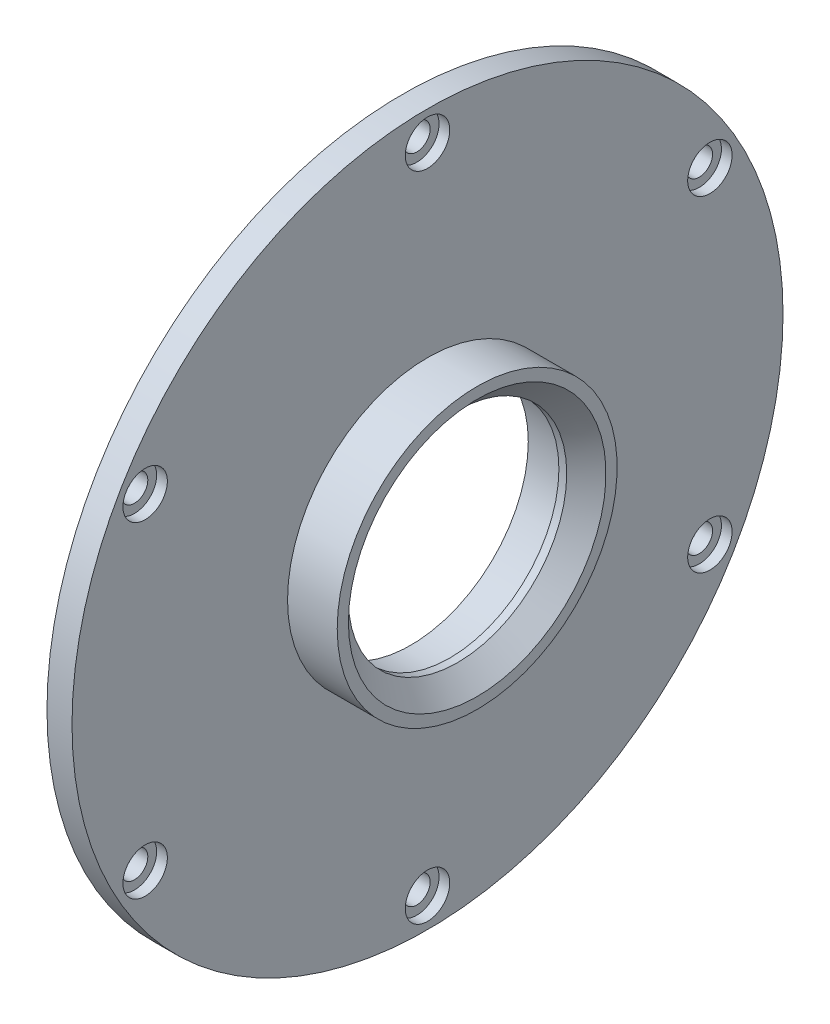
SolidWorks part; units mm, degrees
ref_plane "Front Plane" through (0, 0, 0) normal (0, 0, 1) x (1, 0, 0)
ref_plane "Top Plane" through (0, 0, 0) normal (0, 1, 0) x (1, 0, 0)
ref_plane "Right Plane" through (0, 0, 0) normal (1, 0, 0) x (0, 0, -1)
sketch "Sketch2" plane through (0, 0, 0) normal (0, 0, 1) x (1, 0, 0)
  line L0 (0, 0) -> (58.591, 0) construction
  line L2 (0, 0) -> (18.4, 0)
  line L3 (0, 0) -> (0, 2.5)
  line L4 (0, 2.5) -> (18.4, 2.5)
  line L5 (18.4, 0) -> (18.4, 2.5)
  line L6 (6.0094, 2.5) -> (6.0094, 6)
  line L11 (6.0094, 6) -> (9.9794, 6)
  line L16 (12.9794, 6) -> (12.9794, 3)
  line L17 (12.9794, 3) -> (13.6398, 3)
  line L18 (13.6398, 3) -> (13.6398, 2.5)
  line L19 (13.6398, 2.5) -> (6.0094, 2.5)
  line L22 (13.6398, 2.5) -> (16.1198, 2.5)
  line L23 (13.6398, 2.5) -> (13.6398, 4)
  line L24 (13.6398, 4) -> (16.1198, 4)
  line L25 (16.1198, 2.5) -> (16.1198, 4)
  line L27 (6.0094, 6) -> (9.9794, 6)
  line L28 (6.0094, 6) -> (6.0094, 9)
  line L29 (6.0094, 9) -> (9.9794, 9)
  line L30 (9.9794, 6) -> (9.9794, 9)
  line L31 (6.0094, 9) -> (6.0094, 8.25)
  line L32 (6.0094, 8.25) -> (5.0094, 8.25)
  line L33 (8.6609, 22.001) -> (8.6609, 12.476) construction
  line L34 (5.0094, 12.476) -> (12.3124, 12.476)
  line L35 (9.9794, 9) -> (12.3124, 9)
  line L36 (5.0094, 7.9375) -> (1.8344, 7.9375)
  line L37 (5.0094, 8.25) -> (5.0094, 12.476)
  line L38 (5.0094, 7.9375) -> (5.0094, 13.9365)
  line L39 (5.0094, 13.9365) -> (1.8344, 13.9365)
  line L40 (1.8344, 7.9375) -> (1.8344, 13.9365)
  line L41 (5.0094, 22.001) -> (12.3124, 22.001)
  line L42 (5.0094, 22.001) -> (5.0094, 30.1625)
  line L43 (5.0094, 30.1625) -> (12.3124, 30.1625)
  line L44 (12.3124, 22.001) -> (12.3124, 30.1625)
  line L49 (16.6398, 22.001) -> (16.6398, 7.5)
  line L51 (23.0198, 7.5) -> (23.0198, 6.5)
  line L54 (16.1198, 4) -> (13.6398, 4)
  line L56 (18.0398, 7.5) -> (23.0198, 7.5)
  line L57 (13.3124, 22.001) -> (16.6398, 22.001)
  line L58 (16.1198, 3.5) -> (20.0198, 3.5)
  line L59 (29.9098, 14) -> (26.9098, 11)
  line L60 (4.0094, 31.75) -> (18.0398, 31.75)
  line L61 (18.0398, 7.5) -> (23.0198, 7.5)
  line L62 (18.0398, 7.5) -> (18.0398, 12)
  line L63 (18.0398, 12) -> (23.0198, 12)
  line L64 (23.0198, 7.5) -> (23.0198, 12)
  line L65 (18.0398, 31.75) -> (18.0398, 12)
  line L66 (23.0198, 11) -> (26.9098, 11)
  line L67 (34.8098, 23) -> (31.3098, 19.5)
  line L68 (35.8098, 31) -> (38.7998, 33.99)
  line L69 (29.9098, 14) -> (29.9098, 15)
  line L70 (29.9098, 15) -> (22.9398, 15)
  line L71 (22.9398, 15) -> (21.0398, 15)
  line L72 (18.0398, 7.5) -> (16.6398, 7.5)
  line L73 (21.0398, 15) -> (21.0398, 43)
  line L74 (19.5798, 40) -> (9.6198, 40)
  line L75 (9.6198, 40) -> (4.0094, 40)
  line L76 (21.0398, 43) -> (19.5798, 43)
  line L77 (22.9398, 15) -> (29.9098, 15)
  line L78 (22.9398, 15) -> (22.9398, 21)
  line L79 (22.9398, 21) -> (29.9098, 21)
  line L80 (29.9098, 15) -> (29.9098, 21)
  line L81 (9.6198, 40) -> (19.5798, 40)
  line L82 (9.6198, 40) -> (9.6198, 50)
  line L83 (9.6198, 50) -> (19.5798, 50)
  line L84 (19.5798, 40) -> (19.5798, 50)
  line L85 (4.0094, 40) -> (4.0094, 31.75)
  line L86 (12.9794, 3) -> (12.9794, 2.5)
  line L87 (31.3098, 19.5) -> (29.9098, 19.5)
  line L88 (21.4694, 63.5) -> (21.4694, 51.308)
  line L89 (21.4694, 63.5) -> (25.9398, 63.5)
  line L90 (25.9398, 63.5) -> (25.9398, 25)
  line L91 (27.8398, 25) -> (25.9398, 25)
  line L92 (9.6198, 48) -> (8.1598, 48)
  line L93 (8.1598, 48) -> (8.1598, 53.476)
  line L94 (8.1598, 53.476) -> (19.5798, 53.476)
  line L95 (19.5798, 53.476) -> (19.5798, 50)
  line L96 (13.8698, 63.001) -> (13.8698, 53.476) construction
  line L97 (8.1598, 63.001) -> (19.5798, 63.001)
  line L98 (8.1598, 63.001) -> (8.1598, 68.2625)
  line L99 (8.1598, 68.2625) -> (19.5798, 68.2625)
  line L100 (19.5798, 63.001) -> (19.5798, 68.2625)
  line L101 (12.9794, 6) -> (11.9794, 6)
  line L102 (8.1598, 44.825) -> (4.9848, 44.825)
  line L103 (8.1598, 44.825) -> (8.1598, 54.9365)
  line L104 (8.1598, 54.9365) -> (4.9848, 54.9365)
  line L106 (9.9794, 6) -> (10.8794, 6)
  line L107 (27.8398, 25) -> (34.8098, 25)
  line L108 (34.8098, 25) -> (34.8098, 23)
  line L109 (0, 0) -> (-2, 0)
  line L110 (0, 0) -> (0, 11)
  line L111 (27.8398, 25) -> (34.8098, 25)
  line L112 (27.8398, 25) -> (27.8398, 32.5)
  line L113 (27.8398, 32.5) -> (34.8098, 32.5)
  line L114 (34.8098, 25) -> (34.8098, 32.5)
  line L115 (35.8098, 31) -> (34.8098, 31)
  line L116 (27.8398, 32.5) -> (27.8398, 64.5)
  line L117 (20.5373, 74.025) -> (6.2023, 74.025)
  line L118 (6.2023, 74.025) -> (6.2023, 76.2)
  line L119 (38.7998, 47.29) -> (30.8398, 55.25)
  line L120 (0, 11) -> (-2, 11)
  line L121 (38.7998, 43.815) -> (30.8623, 43.815)
  line L123 (-4.8152, 69.85) -> (1.5348, 76.2)
  line L124 (38.7998, 47.29) -> (38.7998, 33.99)
  line L125 (-2, 0) -> (-2, 11)
  line L126 (38.7998, 37.465) -> (30.8623, 37.465)
  line L127 (30.8623, 43.815) -> (30.8623, 37.465)
  line L128 (6.0094, 2.5) -> (6.0094, 0)
  line L129 (-0.0152, 63.5) -> (-0.0152, 30)
  line L132 (4.9848, 63.5) -> (-0.0152, 63.5)
  line L136 (-1.8152, 30) -> (-11.7752, 30)
  line L138 (-13.7752, 25.4) -> (-2, 25.4)
  line L139 (-2, 25.4) -> (-2, 11.5)
  line L140 (27.8398, 64.5) -> (20.5373, 64.5)
  line L141 (-1.8152, 30) -> (-11.7752, 30)
  line L142 (-1.8152, 30) -> (-1.8152, 39)
  line L143 (-1.8152, 39) -> (-11.7752, 39)
  line L144 (-11.7752, 30) -> (-11.7752, 39)
  line L145 (20.5373, 64.5) -> (20.5373, 74.025)
  line L146 (-12.7752, 37) -> (-12.7752, 47.29)
  line L147 (-12.7752, 37) -> (-11.7752, 37)
  line L148 (30.8398, 55.25) -> (30.8398, 76.2)
  line L149 (11.9794, 6) -> (11.9794, 5.45)
  line L154 (-2, 11.5) -> (0.5, 11.5)
  line L155 (4.9848, 60.6197) -> (24.0348, 60.6197)
  line L160 (4.9848, 60.6197) -> (4.9848, 55.8572)
  line L161 (4.9848, 55.8572) -> (24.0348, 55.8572)
  line L166 (24.0348, 60.6197) -> (24.0348, 55.8572)
  line L167 (4.9848, 60.6197) -> (24.0348, 55.8572) construction
  line L172 (4.9848, 55.8572) -> (24.0348, 60.6197) construction
  line L173 (24.0348, 62.2072) -> (25.9398, 62.2072)
  line L174 (11.9794, 5.45) -> (10.8794, 5.45)
  line L175 (10.8794, 6) -> (10.8794, 5.45)
  line L176 (24.0348, 62.2072) -> (24.0348, 54.2697)
  line L177 (24.0348, 54.2697) -> (25.9398, 54.2697)
  line L178 (25.9398, 62.2072) -> (25.9398, 54.2697)
  line L179 (24.0348, 62.2072) -> (25.9398, 54.2697) construction
  line L180 (24.0348, 54.2697) -> (25.9398, 62.2072) construction
  line L181 (3, 19.6197) -> (15.7, 19.6197)
  line L182 (3, 19.6197) -> (3, 14.8572)
  line L183 (3, 14.8572) -> (15.7, 14.8572)
  line L184 (15.7, 19.6197) -> (15.7, 14.8572)
  line L185 (3, 19.6197) -> (15.7, 14.8572) construction
  line L186 (3, 14.8572) -> (15.7, 19.6197) construction
  line L187 (15.7, 21.2072) -> (16.6398, 21.2072)
  line L188 (15.7, 21.2072) -> (15.7, 13.2697)
  line L189 (15.7, 13.2697) -> (16.6398, 13.2697)
  line L190 (16.6398, 21.2072) -> (16.6398, 13.2697)
  line L191 (15.7, 21.2072) -> (16.6398, 13.2697) construction
  line L192 (15.7, 13.2697) -> (16.6398, 21.2072) construction
  line L193 (0.5, 11.5) -> (0.5, 6.9375)
  line L194 (0.5, 6.9375) -> (1.8344, 6.9375)
  line L195 (23.0198, 6.5) -> (20.0198, 3.5)
  line L196 (4.9848, 63.5) -> (4.9848, 54.9365)
  line L197 (3, 43.825) -> (4.9848, 43.825)
  line L198 (1.8344, 6.9375) -> (1.8344, 7.9375)
  line L199 (6.0094, 0) -> (12.9794, 0)
  line L200 (12.9794, 0) -> (12.9794, 2.5)
  line L201 (18.0398, 31.75) -> (18.0398, 35.875)
  line L202 (18.0398, 35.875) -> (21.0398, 35.875)
  line L203 (30.8398, 76.2) -> (6.2023, 76.2)
  line L204 (2.7573, 69.85) -> (7.2023, 69.85) construction
  line L205 (7.2023, 67.4688) -> (26.2523, 67.4688)
  line L206 (7.2023, 74.025) -> (7.2023, 64.5)
  line L207 (7.2023, 64.5) -> (-1.8152, 64.5)
  line L208 (-1.8152, 64.5) -> (-1.8152, 39)
  line L209 (-12.7752, 47.29) -> (-4.8152, 55.25)
  line L210 (-4.8152, 55.25) -> (-4.8152, 69.85)
  line L211 (7.2023, 67.4688) -> (7.2023, 72.2312)
  line L212 (7.2023, 72.2312) -> (26.2523, 72.2313)
  line L213 (26.2523, 67.4688) -> (26.2523, 72.2313)
  line L214 (26.2523, 73.8187) -> (30.8398, 73.8187)
  line L215 (26.2523, 73.8187) -> (26.2523, 65.8813)
  line L216 (26.2523, 65.8813) -> (30.8398, 65.8813)
  line L217 (30.8398, 73.8187) -> (30.8398, 65.8813)
  line L218 (2.7573, 72.2313) -> (24.9823, 72.2313)
  line L219 (2.7573, 72.2313) -> (2.7573, 67.4687)
  line L220 (2.7573, 67.4687) -> (24.9823, 67.4687)
  line L221 (24.9823, 72.2313) -> (24.9823, 67.4687)
  line L222 (24.9823, 69.85) -> (20.5373, 69.85) construction
  line L223 (21.4694, 51.308) -> (22.9398, 51.308)
  line L224 (22.9398, 51.308) -> (22.9398, 21)
  line L225 (13.6398, 4) -> (13.6398, 12.2697)
  line L226 (13.6398, 12.2697) -> (13.3124, 12.2697)
  line L227 (13.3124, 12.2697) -> (13.3124, 22.001)
  line L228 (12.3124, 9) -> (12.3124, 12.476)
  line L229 (-1.8152, 30) -> (-0.0152, 30)
  line L230 (8.1598, 65.6317) -> (2.7573, 65.6317) construction
  line L231 (19.5798, 65.6317) -> (24.9823, 65.6317) construction
  line L232 (1.5348, 76.2) -> (6.2023, 76.2)
  line L233 (-11.7752, 30) -> (-13.7752, 30)
  line L234 (-13.7752, 30) -> (-13.7752, 25.4)
  line L235 (3, 13.9365) -> (3, 43.825)
  line L236 (4.9848, 54.9365) -> (4.9848, 44.825)
  line L237 (4.9848, 43.825) -> (4.9848, 44.825)
  circle A0 centre (26.8898, 25.95) radius 0.95
  circle A1 centre (21.9898, 15.95) radius 0.95
  circle A2 centre (17.3398, 8.2) radius 0.7
  circle A3 centre (10.4294, 6.45) radius 0.45
  circle A4 centre (-0.9152, 30.9) radius 0.9
  point P7 (24.9873, 58.2385)
  point P131 (16.1699, 17.2385)
  point P135 (14.5098, 58.2385)
  point P146 (9.35, 17.2385)
sketch "Sketch3" plane through (0, 0, 0) normal (0, 0, 1) x (1, 0, 0)
  line L0 (34.8098, 25) -> (34.8098, 23) construction
  line L4 (29.9098, 15) -> (29.9098, 21) construction
  line L5 (31.3098, 19.5) -> (29.9098, 19.5) construction
  line L6 (34.8098, 23) -> (31.3098, 19.5) construction
  line L7 (22.9398, 21) -> (29.9098, 21) construction
  line L11 (34.8098, 25) -> (34.8098, 23)
  line L15 (29.9098, 19.5) -> (29.9098, 21)
  line L16 (31.3098, 19.5) -> (29.9098, 19.5)
  line L17 (34.8098, 23) -> (31.3098, 19.5)
  line L18 (22.9398, 21) -> (29.9098, 21)
  line L22 (27.8398, 25) -> (25.9398, 25) construction
  line L23 (27.8398, 25) -> (34.8098, 25) construction
  line L24 (25.9398, 63.5) -> (25.9398, 25) construction
  line L25 (22.9398, 51.308) -> (22.9398, 21) construction
  line L26 (21.4694, 51.308) -> (22.9398, 51.308) construction
  line L27 (21.4694, 63.5) -> (21.4694, 51.308) construction
  line L28 (21.4694, 63.5) -> (25.9398, 63.5) construction
  line L29 (27.8398, 25) -> (25.9398, 25)
  line L30 (27.8398, 25) -> (34.8098, 25)
  line L31 (25.9398, 63.5) -> (25.9398, 25)
  line L32 (22.9398, 51.308) -> (22.9398, 21)
  line L33 (21.4694, 51.308) -> (22.9398, 51.308)
  line L34 (21.4694, 63.5) -> (21.4694, 51.308)
  line L35 (21.4694, 63.5) -> (25.9398, 63.5)
revolve "Revolve1" add sketch "Sketch3" angle 360 about L0
sketch "Sketch4" plane through (0, 0, 0) normal (1, 0, 0) x (0, 0, -1)
  line L0 (0, 0) -> (0, 69.85) construction
  line L1 (0, 0) -> (13.6271, 68.5079) construction
  line L2 (0, 0) -> (0, 58.2385) construction
  line L3 (0, 0) -> (50.436, 29.1192) construction
  line L4 (0, 0) -> (0, 31.75) construction
  line L5 (0, 0) -> (12.1502, 29.3332) construction
  line L6 (0, 0) -> (0, 17.2385) construction
  line L7 (0, 0) -> (14.929, 8.6192) construction
  line L8 (0, 0) -> (0, 58.2385) construction
  line L9 (0, 0) -> (50.436, 29.1192) construction
  line L10 (0, 0) -> (5.9583, 29.9542) construction
  line L11 (0, 0) -> (16.9677, 25.394) construction
  circle A0 centre (0, 0) radius 69.85 construction
  circle A1 centre (0, 0) radius 58.2385 construction
  circle A2 centre (0, 0) radius 31.75 construction
  circle A3 centre (0, 0) radius 17.2385 construction
  circle A4 centre (0, 69.85) radius 3.175
  circle A5 centre (0, 58.2385) radius 4.7625
  circle A6 centre (0, 31.75) radius 3.175
  circle A7 centre (0, 17.2385) radius 4.7625
  circle A8 centre (13.6271, 68.5079) radius 3.175
  circle A9 centre (26.7304, 64.533) radius 3.175
  circle A10 centre (38.8066, 58.0782) radius 3.175
  circle A11 centre (49.3914, 49.3914) radius 3.175
  circle A12 centre (58.0782, 38.8066) radius 3.175
  circle A13 centre (64.533, 26.7304) radius 3.175
  circle A14 centre (68.5079, 13.6271) radius 3.175
  circle A15 centre (69.85, 0) radius 3.175
  circle A16 centre (68.5079, -13.6271) radius 3.175
  circle A17 centre (64.533, -26.7304) radius 3.175
  circle A18 centre (58.0782, -38.8066) radius 3.175
  circle A19 centre (49.3914, -49.3914) radius 3.175
  circle A20 centre (38.8066, -58.0782) radius 3.175
  circle A21 centre (26.7304, -64.533) radius 3.175
  circle A22 centre (13.6271, -68.5079) radius 3.175
  circle A23 centre (0, -69.85) radius 3.175
  circle A24 centre (-13.6271, -68.5079) radius 3.175
  circle A25 centre (-26.7304, -64.533) radius 3.175
  circle A26 centre (-38.8066, -58.0782) radius 3.175
  circle A27 centre (-49.3914, -49.3914) radius 3.175
  circle A28 centre (-58.0782, -38.8066) radius 3.175
  circle A29 centre (-64.533, -26.7304) radius 3.175
  circle A30 centre (-68.5079, -13.6271) radius 3.175
  circle A31 centre (-69.85, 0) radius 3.175
  circle A32 centre (-68.5079, 13.6271) radius 3.175
  circle A33 centre (-64.533, 26.7304) radius 3.175
  circle A34 centre (-58.0782, 38.8066) radius 3.175
  circle A35 centre (-49.3914, 49.3914) radius 3.175
  circle A36 centre (-38.8066, 58.0782) radius 3.175
  circle A37 centre (-26.7304, 64.533) radius 3.175
  circle A38 centre (-13.6271, 68.5079) radius 3.175
  circle A47 centre (50.436, 29.1192) radius 4.7625
  circle A48 centre (50.436, -29.1192) radius 4.7625
  circle A49 centre (0, -58.2385) radius 4.7625
  circle A50 centre (-50.436, -29.1192) radius 4.7625
  circle A51 centre (-50.436, 29.1192) radius 4.7625
  circle A58 centre (12.1502, 29.3332) radius 3.175
  circle A59 centre (22.4506, 22.4506) radius 3.175
  circle A60 centre (29.3332, 12.1502) radius 3.175
  circle A61 centre (31.75, 0) radius 3.175
  circle A62 centre (29.3332, -12.1502) radius 3.175
  circle A63 centre (22.4506, -22.4506) radius 3.175
  circle A64 centre (12.1502, -29.3332) radius 3.175
  circle A65 centre (0, -31.75) radius 3.175
  circle A66 centre (-12.1502, -29.3332) radius 3.175
  circle A67 centre (-22.4506, -22.4506) radius 3.175
  circle A68 centre (-29.3332, -12.1502) radius 3.175
  circle A69 centre (-31.75, 0) radius 3.175
  circle A70 centre (-29.3332, 12.1502) radius 3.175
  circle A71 centre (-22.4506, 22.4506) radius 3.175
  circle A72 centre (14.929, 8.6192) radius 4.7625
  circle A73 centre (14.929, -8.6192) radius 4.7625
  circle A74 centre (0, -17.2385) radius 4.7625
  circle A75 centre (-14.929, -8.6192) radius 4.7625
  circle A76 centre (-14.929, 8.6192) radius 4.7625
  circle A77 centre (0, 0) radius 50
  circle A78 centre (0, 0) radius 9
  circle A79 centre (-12.1502, 29.3332) radius 3.175
  circle A80 centre (0, 0) radius 76.2
  circle A81 centre (0, 0) radius 74.025
  circle A82 centre (0, 69.85) radius 3.9687
  circle A83 centre (49.3914, 49.3914) radius 3.9687
  circle A84 centre (69.85, 0) radius 3.9688
  circle A85 centre (49.3914, -49.3914) radius 3.9687
  circle A86 centre (0, -69.85) radius 3.9687
  circle A87 centre (-49.3914, -49.3914) radius 3.9687
  circle A88 centre (-69.85, 0) radius 3.9688
  circle A89 centre (-49.3914, 49.3914) radius 3.9687
  circle A90 centre (0, 69.85) radius 2.3812
  circle A91 centre (13.6271, 68.5079) radius 2.3812
  circle A92 centre (26.7304, 64.533) radius 2.3813
  circle A93 centre (38.8066, 58.0782) radius 2.3812
  circle A94 centre (49.3914, 49.3914) radius 2.3812
  circle A95 centre (58.0782, 38.8066) radius 2.3812
  circle A96 centre (64.533, 26.7304) radius 2.3813
  circle A97 centre (68.5079, 13.6271) radius 2.3813
  circle A98 centre (69.85, 0) radius 2.3813
  circle A99 centre (68.5079, -13.6271) radius 2.3813
  circle A100 centre (64.533, -26.7304) radius 2.3813
  circle A101 centre (58.0782, -38.8066) radius 2.3812
  circle A102 centre (49.3914, -49.3914) radius 2.3812
  circle A103 centre (38.8066, -58.0782) radius 2.3812
  circle A104 centre (26.7304, -64.533) radius 2.3813
  circle A105 centre (13.6271, -68.5079) radius 2.3812
  circle A106 centre (0, -69.85) radius 2.3812
  circle A107 centre (-13.6271, -68.5079) radius 2.3812
  circle A108 centre (-26.7304, -64.533) radius 2.3813
  circle A109 centre (-38.8066, -58.0782) radius 2.3812
  circle A110 centre (-49.3914, -49.3914) radius 2.3812
  circle A111 centre (-58.0782, -38.8066) radius 2.3812
  circle A112 centre (-64.533, -26.7304) radius 2.3812
  arc A113 (3.0399, 30.8338) -> (8.9911, 29.65) centre (5.9583, 29.9542) cw
  arc A114 (14.6081, 27.3234) -> (19.6532, 23.9523) centre (16.9677, 25.394) cw
  arc A115 (23.9523, 19.6532) -> (27.3234, 14.6081) centre (25.394, 16.9677) cw
  arc A116 (29.65, 8.9911) -> (30.8338, 3.0399) centre (29.9542, 5.9583) cw
  arc A117 (30.8338, -3.0399) -> (29.65, -8.9911) centre (29.9542, -5.9583) cw
  arc A118 (27.3234, -14.6081) -> (23.9523, -19.6532) centre (25.394, -16.9677) cw
  arc A119 (19.6532, -23.9523) -> (14.6081, -27.3234) centre (16.9677, -25.394) cw
  arc A120 (8.9911, -29.65) -> (3.0399, -30.8338) centre (5.9583, -29.9542) cw
  arc A121 (-3.0399, -30.8338) -> (-8.9911, -29.65) centre (-5.9583, -29.9542) cw
  arc A122 (-14.6081, -27.3234) -> (-19.6532, -23.9523) centre (-16.9677, -25.394) cw
  arc A123 (-23.9523, -19.6532) -> (-27.3234, -14.6081) centre (-25.394, -16.9677) cw
  arc A124 (-29.65, -8.9911) -> (-30.8338, -3.0399) centre (-29.9542, -5.9583) cw
  arc A125 (-30.8338, 3.0399) -> (-29.65, 8.9911) centre (-29.9542, 5.9583) cw
  arc A126 (-27.3234, 14.6081) -> (-23.9523, 19.6532) centre (-25.394, 16.9677) cw
  arc A127 (-19.6532, 23.9523) -> (-14.6081, 27.3234) centre (-16.9677, 25.394) cw
  arc A128 (-8.9911, 29.65) -> (-3.0399, 30.8338) centre (-5.9583, 29.9542) cw
  arc A129 (26.9875, 0) -> (26.9932, 0.1932) centre (30.2705, 0) cw
  arc A130 (65.0988, 0.2771) -> (65.0875, 0) centre (68.4964, 0) ccw
  circle A131 centre (1.5875, 0) radius 40
  circle A132 centre (1.5875, 0) radius 2.5
  circle A133 centre (1.5875, 0) radius 3
  circle A134 centre (1.5875, 0) radius 43
  circle A135 centre (-68.5079, -13.6271) radius 2.3813
  circle A136 centre (-69.85, 0) radius 2.3813
  circle A137 centre (-68.5079, 13.6271) radius 2.3813
  circle A138 centre (-64.533, 26.7304) radius 2.3812
  circle A139 centre (-58.0782, 38.8066) radius 2.3812
  circle A140 centre (-49.3914, 49.3914) radius 2.3812
  circle A141 centre (-38.8066, 58.0782) radius 2.3812
  circle A142 centre (-26.7304, 64.533) radius 2.3813
  circle A143 centre (-13.6271, 68.5079) radius 2.3812
  circle A144 centre (0, 58.2385) radius 2.3812
  circle A145 centre (0, 58.2385) radius 3.9688
  circle A146 centre (50.436, 29.1192) radius 3.9688
  circle A147 centre (50.436, 29.1192) radius 2.3813
  circle A148 centre (50.436, -29.1192) radius 3.9687
  circle A149 centre (50.436, -29.1192) radius 2.3812
  circle A150 centre (0, -58.2385) radius 3.9687
  circle A151 centre (0, -58.2385) radius 2.3812
  circle A152 centre (-50.436, -29.1192) radius 3.9687
  circle A153 centre (-50.436, -29.1192) radius 2.3812
  circle A154 centre (-50.436, 29.1192) radius 3.9687
  circle A155 centre (-50.436, 29.1192) radius 2.3812
  spline S1 degree 4 poles (26.9875, 0) (26.9875, -0.0248) (26.9882, -0.0743) (26.9912, -0.1613) (26.9992, -0.2849) (27.0142, -0.4323) (27.0403, -0.5994) (27.0821, -0.7965) (27.1455, -1.0177) (27.2241, -1.2336) (27.3173, -1.4437) (27.4329, -1.6623) (27.5739, -1.8864) (27.7427, -2.1125) (27.9417, -2.3365) (28.1305, -2.5184) (28.3007, -2.6647) (28.4457, -2.7828) (28.5617, -2.8775) (28.6745, -2.9758) (28.7813, -3.0807) (28.9057, -3.2206) (29.0482, -3.4108) (29.197, -3.6576) (29.3758, -4.0447) (29.5291, -4.5502) (29.6152, -5.1612) (29.5933, -5.8758) (29.4507, -6.5869) (29.186, -7.2733) (28.8461, -7.831) (28.4818, -8.2549) (28.1375, -8.5536) (27.8792, -8.7284) (27.6484, -8.8496) (27.4154, -8.9438) (27.2144, -9.0029) (27.0118, -9.0554) (26.7709, -9.1263) (26.5334, -9.2082) (26.2634, -9.3231) (25.9685, -9.4827) (25.5538, -9.7623) (25.0678, -10.2216) (24.6281, -10.8948) (24.3613, -11.7878) (24.3459, -12.6097) (24.4764, -13.2366) (24.6525, -13.7006) (24.8058, -14.0202) (24.9382, -14.271) (25.0503, -14.5321) (25.1258, -14.8064) (25.1736, -15.0995) (25.1911, -15.4094) (25.1742, -15.8163) (25.0891, -16.3148) (24.907, -16.8764) (24.5182, -17.6315) (23.9757, -18.2942) (23.3695, -18.7764) (22.7564, -19.084) (22.3641, -19.2199) (22.0554, -19.2923) (21.7533, -19.3289) (21.4612, -19.3296) (21.1723, -19.2896) (20.8852, -19.2417) (20.5956, -19.2104) (20.3043, -19.1994) (19.8669, -19.2177) (19.2899, -19.3231) (18.5833, -19.6092) (17.8444, -20.1834) (17.3807, -20.828) (17.1316, -21.424) (17.0182, -21.8879) (16.9714, -22.1971) (16.9537, -22.4701) (16.9533, -22.7044) (16.9619, -22.9384) (16.9737, -23.1333) (16.977, -23.3286) (16.9594, -23.5624) (16.9177, -23.8101) (16.834, -24.1055) (16.6578, -24.5276) (16.3623, -25.0151) (15.9278, -25.5198) (15.3432, -25.99) (14.6957, -26.3472) (14.0068, -26.5857) (13.3856, -26.6851) (12.847, -26.6849) (12.4166, -26.6224) (12.1324, -26.5468) (11.9058, -26.4598) (11.7342, -26.3753) (11.6017, -26.2989) (11.4727, -26.2169) (11.3444, -26.1337) (11.1825, -26.0322) (10.9836, -25.9179) (10.7435, -25.7991) (10.4587, -25.6867) (10.0106, -25.5536) (9.3843, -25.468) (8.599, -25.5363) (7.7243, -25.8773) (7.1093, -26.3459) (6.716, -26.8042) (6.4745, -27.1841) (6.3352, -27.4489) (6.215, -27.7227) (6.1113, -28.0028) (5.9959, -28.2789) (5.841, -28.5357) (5.6522, -28.7792) (5.4316, -29.007) (5.1188, -29.2711) (4.6965, -29.5439) (4.1624, -29.7882) (3.5487, -29.9564) (2.9521, -30.0296) (2.386, -30.0225) (1.8595, -29.949) (1.3409, -29.8055) (0.9058, -29.6147) (0.5544, -29.4004) (0.2828, -29.1832) (0.0847, -28.9875) (-0.0865, -28.768) (-0.2353, -28.5332) (-0.3904, -28.3016) (-0.5598, -28.0786) (-0.792, -27.8146) (-1.1036, -27.5274) (-1.5105, -27.2448) (-2.0688, -26.9834) (-2.7167, -26.8202) (-3.459, -26.7949) (-4.1529, -26.9407) (-4.7224, -27.1899) (-5.1296, -27.455) (-5.3866, -27.661) (-5.5925, -27.8507) (-5.7558, -28.014) (-5.9199, -28.1766) (-6.0977, -28.3246) (-6.3382, -28.4851) (-6.6906, -28.6628) (-7.1669, -28.8182) (-7.7668, -28.9076) (-8.4201, -28.8957) (-9.0747, -28.7804) (-9.7144, -28.5614) (-10.3217, -28.2381) (-10.8061, -27.8636) (-11.1671, -27.4837) (-11.4143, -27.1402) (-11.5734, -26.859) (-11.6946, -26.573) (-11.7735, -26.2857) (-11.8173, -25.9915) (-11.8668, -25.6988) (-11.9353, -25.4093) (-12.0257, -25.1261) (-12.198, -24.7091) (-12.5089, -24.187) (-13.0379, -23.6191) (-13.8448, -23.1355) (-14.6072, -22.9365) (-15.2369, -22.9149) (-15.701, -22.9694) (-16.0024, -23.0316) (-16.2609, -23.107) (-16.4782, -23.1841) (-16.6576, -23.2529) (-16.8015, -23.307) (-16.9839, -23.3672) (-17.2087, -23.4203) (-17.4853, -23.4534) (-17.811, -23.4543) (-18.2291, -23.4104) (-18.7305, -23.2885) (-19.2884, -23.06) (-19.8603, -22.7052) (-20.3581, -22.2764) (-20.7758, -21.7899) (-21.1086, -21.2598) (-21.3336, -20.7318) (-21.4619, -20.2263) (-21.5006, -19.8113) (-21.4889, -19.4989) (-21.4468, -19.2424) (-21.3965, -19.0408) (-21.34, -18.8332) (-21.2878, -18.6168) (-21.2341, -18.3322) (-21.1962, -17.9773) (-21.1985, -17.5604) (-21.2781, -17.0173) (-21.4721, -16.4256) (-21.838, -15.7861) (-22.3482, -15.2578) (-22.8946, -14.8957) (-23.3828, -14.6878) (-23.7368, -14.5834) (-24.0536, -14.5215) (-24.3285, -14.4876) (-24.6045, -14.47) (-24.8811, -14.458) (-25.1556, -14.4184) (-25.4228, -14.3439) (-25.6932, -14.2375) (-26.1109, -14.0218) (-26.5677, -13.6822) (-27.0258, -13.1981) (-27.4314, -12.5682) (-27.7017, -11.9578) (-27.8746, -11.3112) (-27.9332, -10.727) (-27.9111, -10.2247) (-27.8415, -9.8214) (-27.7568, -9.5159) (-27.6427, -9.2298) (-27.5004, -8.9659) (-27.3212, -8.7261) (-27.1301, -8.4966) (-26.9071, -8.1967) (-26.6417, -7.7583) (-26.3997, -7.1508) (-26.2841, -6.3875) (-26.3642, -5.5798) (-26.6019, -4.9055) (-26.9193, -4.3761) (-27.2736, -3.9636) (-27.583, -3.6904) (-27.8719, -3.4871) (-28.1186, -3.3407) (-28.3135, -3.2371) (-28.5043, -3.1411) (-28.6854, -3.0419) (-28.9002, -2.8984) (-29.1355, -2.6958) (-29.4123, -2.3882) (-29.6958, -1.9552) (-29.932, -1.437) (-30.0985, -0.839) (-30.1779, -0.2025) (-30.1603, 0.4599) (-30.0348, 1.1323) (-29.8199, 1.711) (-29.5617, 2.1719) (-29.3035, 2.5118) (-29.0784, 2.748) (-28.8655, 2.924) (-28.6761, 3.0468) (-28.5112, 3.1367) (-28.3775, 3.205) (-28.2106, 3.2911) (-28.0136, 3.4005) (-27.7912, 3.5413) (-27.5508, 3.7219) (-27.2011, 4.0343) (-26.7941, 4.5285) (-26.4419, 5.234) (-26.2777, 6.1494) (-26.351, 6.9081) (-26.5268, 7.4739) (-26.7218, 7.8823) (-26.8619, 8.1196) (-26.9953, 8.3144) (-27.1373, 8.5028) (-27.2613, 8.6553) (-27.3845, 8.8088) (-27.518, 9.0035) (-27.6324, 9.2103) (-27.7412, 9.4693) (-27.8326, 9.7814) (-27.9074, 10.1885) (-27.9345, 10.6913) (-27.8808, 11.2771) (-27.6878, 12.0229) (-27.3166, 12.8111) (-26.8405, 13.4278) (-26.3243, 13.8718) (-25.9118, 14.1263) (-25.6503, 14.2566) (-25.3769, 14.3596) (-25.0933, 14.4318) (-24.8027, 14.4634) (-24.5112, 14.4738) (-24.1629, 14.5033) (-23.7608, 14.5717) (-23.1887, 14.7443) (-22.5511, 15.0901) (-21.962, 15.6231) (-21.544, 16.2749) (-21.3217, 16.857) (-21.2175, 17.3851) (-21.1902, 17.8397) (-21.2185, 18.2374) (-21.2771, 18.5739) (-21.3443, 18.8506) (-21.405, 19.0706) (-21.4579, 19.2928) (-21.4883, 19.5194) (-21.4981, 19.805) (-21.4664, 20.1907) (-21.3565, 20.6672) (-21.1331, 21.2135) (-20.8025, 21.7541) (-20.3882, 22.2461) (-19.8974, 22.677) (-19.3379, 23.033) (-18.7964, 23.2649) (-18.309, 23.3941) (-17.8981, 23.4483) (-17.5726, 23.4572) (-17.2924, 23.4331) (-17.0602, 23.3874) (-16.8337, 23.3199) (-16.6495, 23.2499) (-16.4659, 23.1791) (-16.2424, 23.1025) (-16.0156, 23.0362) (-15.7461, 22.9768) (-15.2967, 22.9185) (-14.7035, 22.9278) (-13.9592, 23.0948) (-13.1407, 23.5365) (-12.5805, 24.0908) (-12.2382, 24.6309) (-12.0505, 25.0599) (-11.9538, 25.3442) (-11.8892, 25.5989) (-11.8463, 25.8198) (-11.8162, 26.0048) (-11.7926, 26.153) (-11.7577, 26.3372) (-11.6989, 26.5548) (-11.5969, 26.8111) (-11.4414, 27.0975) (-11.1977, 27.4473) (-10.8392, 27.8343) (-10.3554, 28.2166) (-9.7549, 28.5431) (-9.1303, 28.7642) (-8.5, 28.8851) (-7.879, 28.911) (-7.3126, 28.8458) (-6.8128, 28.7091) (-6.4345, 28.54) (-6.1692, 28.378) (-5.9665, 28.2173) (-5.8163, 28.0752) (-5.6659, 27.9232) (-5.5067, 27.7699) (-5.2907, 27.5806) (-5.0072, 27.369) (-4.6509, 27.1597) (-4.148, 26.9513) (-3.5452, 26.8146) (-2.8302, 26.7991) (-2.0381, 26.9749) (-1.3495, 27.3225) (-0.8483, 27.741) (-0.5146, 28.1291) (-0.2991, 28.4338) (-0.1401, 28.6862) (0.0331, 28.93) (0.2405, 29.146) (0.4774, 29.3422) (0.7418, 29.5165) (1.1036, 29.7066) (1.5741, 29.882) (2.1471, 30.006) (2.8151, 30.041) (3.4791, 29.9721) (4.2039, 29.7804) (4.8064, 29.4933) (5.2708, 29.1628) (5.6049, 28.8311) (5.7894, 28.6062) (5.9424, 28.3744) (6.0642, 28.1249) (6.161, 27.8653) (6.2635, 27.608) (6.3813, 27.357) (6.5388, 27.0748) (6.7484, 26.7704) (7.0986, 26.3707) (7.6135, 25.9641) (8.2747, 25.644) (8.9962, 25.4959) (9.6181, 25.496) (10.1582, 25.5894) (10.5546, 25.7168) (10.8796, 25.8629) (11.1331, 26.0022) (11.3224, 26.1188) (11.5021, 26.2366) (11.6784, 26.3463) (11.9094, 26.4649) (12.2028, 26.5718) (12.6092, 26.6624) (13.1291, 26.6958) (13.7, 26.6444) (14.3062, 26.4914) (14.8974, 26.2443) (15.459, 25.9029) (15.9732, 25.4681) (16.3631, 25.0071) (16.6337, 24.567) (16.8044, 24.1822) (16.9036, 23.8716) (16.9571, 23.5978) (16.9755, 23.3672) (16.9741, 23.1748) (16.9669, 23.0211) (16.9571, 22.8289) (16.9512, 22.5982) (16.9599, 22.3287) (16.9946, 22.0224) (17.0874, 21.5638) (17.3043, 20.9714) (17.7315, 20.3087) (18.4426, 19.693) (19.1468, 19.3677) (19.739, 19.2351) (20.1882, 19.2012) (20.4852, 19.2034) (20.7812, 19.2282) (21.0745, 19.2719) (21.3675, 19.3208) (21.6648, 19.3336) (21.9737, 19.306) (22.2899, 19.241) (22.6922, 19.1116) (23.1641, 18.8854) (23.669, 18.5404) (24.1634, 18.0628) (24.569, 17.5219) (24.8807, 16.9345) (25.0937, 16.316) (25.184, 15.7743) (25.1924, 15.3317) (25.1581, 14.9969) (25.1154, 14.7695) (25.0522, 14.5468) (24.9658, 14.3321) (24.8616, 14.1257) (24.7568, 13.9198) (24.6402, 13.6649) (24.524, 13.3562) (24.3985, 12.886) (24.3389, 12.2663) (24.4166, 11.5605) (24.6979, 10.7931) (25.0952, 10.2042) (25.5426, 9.7706) (25.9551, 9.4883) (26.2689, 9.3208) (26.5627, 9.1971) (26.83, 9.1062) (27.1019, 9.0315) (27.3749, 8.9598) (27.6385, 8.8574) (27.887, 8.7225) (28.1969, 8.5098) (28.5449, 8.1936) (28.9002, 7.7549) (29.2229, 7.1817) (29.4529, 6.562) (29.5858, 5.9108) (29.6165, 5.2432) (29.5485, 4.659) (29.4188, 4.1725) (29.2636, 3.7931) (29.1144, 3.5129) (28.9404, 3.2582) (28.7432, 3.0317) (28.5155, 2.8371) (28.281, 2.6515) (28.0578, 2.4519) (27.8492, 2.2371) (27.6347, 1.9761) (27.4574, 1.7102) (27.3152, 1.4444) (27.2047, 1.1845) (27.1307, 0.9703) (27.0789, 0.7793) (27.0441, 0.6164) (27.021, 0.472) (27.0061, 0.351) (26.9981, 0.2662) (26.9946, 0.2176) (26.9932, 0.1932) knots 0.06864 0.06864 0.06864 0.06864 0.06864 0.069106 0.069571 0.070037 0.070502 0.071433 0.072364 0.073295 0.074226 0.075157 0.076088 0.077301 0.078514 0.079727 0.08094 0.081547 0.082153 0.08276 0.083366 0.083973 0.084579 0.085792 0.087214 0.088636 0.091479 0.094323 0.097166 0.100174 0.103182 0.10619 0.107694 0.109198 0.110555 0.111234 0.111912 0.113269 0.113948 0.114626 0.115983 0.11734 0.118697 0.120055 0.12408 0.128106 0.131537 0.134967 0.137266 0.138415 0.139565 0.140714 0.141863 0.143013 0.144162 0.145524 0.146885 0.149608 0.152331 0.155054 0.160594 0.163364 0.164749 0.166134 0.167314 0.168495 0.169675 0.170855 0.172035 0.173215 0.174395 0.175575 0.179125 0.182676 0.186612 0.190548 0.191813 0.193079 0.194345 0.195611 0.196244 0.196877 0.198142 0.198775 0.199408 0.200674 0.202207 0.203741 0.206808 0.209874 0.212941 0.21584 0.218738 0.221637 0.223086 0.224535 0.225775 0.226394 0.227014 0.227634 0.228253 0.228873 0.229493 0.230732 0.231971 0.233211 0.23445 0.238303 0.242155 0.245814 0.249472 0.250683 0.251894 0.253105 0.254316 0.255527 0.256738 0.257949 0.25916 0.260514 0.261868 0.264577 0.267285 0.269993 0.272142 0.27429 0.276439 0.278588 0.280839 0.281965 0.283091 0.284217 0.285343 0.286469 0.287595 0.288737 0.289879 0.292163 0.294447 0.296732 0.299827 0.302922 0.306383 0.308113 0.309844 0.31078 0.311716 0.312652 0.313588 0.314524 0.31546 0.317332 0.319969 0.322606 0.325244 0.327881 0.330703 0.333524 0.336346 0.337757 0.339168 0.340372 0.341576 0.34278 0.343984 0.345188 0.346392 0.347596 0.3488 0.352495 0.356189 0.36002 0.36385 0.365096 0.366342 0.367588 0.368834 0.369457 0.370079 0.370702 0.371325 0.372571 0.373817 0.375207 0.376596 0.379375 0.382154 0.384933 0.387459 0.389986 0.392513 0.39504 0.396723 0.398407 0.399249 0.400091 0.400932 0.401774 0.402737 0.4037 0.405625 0.407551 0.409476 0.412569 0.415662 0.41939 0.421254 0.423119 0.42424 0.425361 0.426483 0.427604 0.428726 0.429847 0.430969 0.43209 0.433431 0.437455 0.440138 0.44282 0.445528 0.448236 0.450943 0.452297 0.453651 0.454862 0.456073 0.457284 0.458495 0.459706 0.460916 0.463338 0.466783 0.470228 0.473297 0.476366 0.478273 0.480179 0.482085 0.483038 0.483991 0.484828 0.485664 0.486501 0.487337 0.48901 0.490683 0.493189 0.495695 0.498202 0.500708 0.503552 0.506397 0.509241 0.510663 0.512085 0.513303 0.514521 0.51513 0.515738 0.516347 0.516956 0.518174 0.519391 0.520609 0.521827 0.525766 0.529706 0.533208 0.53671 0.537985 0.53926 0.540535 0.541173 0.54181 0.543085 0.543723 0.54436 0.545635 0.54691 0.548267 0.549623 0.552335 0.555047 0.55776 0.562061 0.566363 0.567545 0.568728 0.56991 0.571092 0.572275 0.573457 0.574639 0.575822 0.577939 0.580057 0.584292 0.587472 0.590653 0.592493 0.594334 0.596174 0.598014 0.59894 0.599865 0.60079 0.601715 0.60264 0.603565 0.605415 0.607973 0.610531 0.61309 0.615648 0.618364 0.62108 0.623796 0.625154 0.626512 0.627788 0.629065 0.629703 0.630341 0.631618 0.632256 0.632895 0.634171 0.635448 0.636724 0.640232 0.643739 0.647674 0.651609 0.652825 0.65404 0.655256 0.656472 0.65708 0.657688 0.658296 0.658904 0.66012 0.661336 0.662756 0.664177 0.667018 0.669858 0.672699 0.675209 0.677718 0.680227 0.682736 0.684412 0.686087 0.686924 0.687762 0.688599 0.689437 0.690391 0.691345 0.693254 0.695162 0.697071 0.700143 0.703216 0.706655 0.710095 0.712514 0.713723 0.714933 0.716142 0.717352 0.718561 0.719771 0.721123 0.722475 0.725179 0.727883 0.730587 0.733273 0.735959 0.739989 0.741332 0.742455 0.743577 0.7447 0.745823 0.746945 0.748068 0.749191 0.750314 0.752181 0.754048 0.757782 0.760871 0.763961 0.765883 0.767806 0.769729 0.77069 0.771651 0.772492 0.773333 0.774174 0.775015 0.776698 0.77838 0.780903 0.783427 0.785951 0.788475 0.791257 0.794039 0.796822 0.798213 0.799604 0.800852 0.802099 0.802723 0.803347 0.803971 0.804595 0.805842 0.80709 0.808337 0.809585 0.81342 0.817255 0.820945 0.824634 0.825837 0.827039 0.828242 0.829444 0.830647 0.831849 0.833052 0.834254 0.835663 0.837072 0.83989 0.842708 0.845526 0.848167 0.850807 0.853447 0.856087 0.857024 0.857961 0.858897 0.859834 0.860771 0.861707 0.862644 0.863581 0.865314 0.867048 0.870515 0.873613 0.876711 0.880181 0.881916 0.883651 0.884794 0.885937 0.887081 0.888224 0.889367 0.89051 0.891653 0.892797 0.895451 0.898105 0.90076 0.903414 0.906126 0.908838 0.911549 0.912905 0.914261 0.915474 0.916686 0.917899 0.919111 0.920323 0.921536 0.922748 0.923961 0.925793 0.926709 0.927625 0.928541 0.929457 0.929915 0.930373 0.930831 0.931289 0.931289 0.931289 0.931289 0.931289
  spline S3 degree 4 poles (65.0875, 0) (65.0875, -0.2085) (65.1336, -0.6093) (65.3196, -1.4523) (65.739, -2.0447) (66.242, -2.6341) (66.7299, -3.0916) (67.1731, -3.6257) (67.5219, -4.2566) (67.8399, -5.1354) (68.0042, -6.2629) (67.9043, -7.3956) (67.5534, -8.464) (67.1166, -9.2437) (66.7001, -9.7852) (66.2223, -10.2316) (65.7042, -10.5824) (65.1033, -10.9671) (64.5015, -11.4984) (63.9836, -12.2541) (63.7076, -13.0981) (63.6577, -13.8665) (63.7509, -14.5541) (63.9279, -15.1344) (64.2231, -15.7099) (64.6171, -16.2749) (64.9859, -16.8848) (65.2405, -17.5795) (65.3772, -18.3315) (65.3953, -19.1188) (65.2888, -19.9454) (65.0416, -20.7887) (64.6379, -21.6235) (64.0595, -22.4019) (63.3699, -23.0372) (62.5888, -23.4701) (61.782, -23.7464) (61.0578, -24.1183) (60.3658, -24.7064) (59.8816, -25.4078) (59.6093, -26.1527) (59.5127, -26.9191) (59.5498, -27.5888) (59.7273, -28.2781) (60.0289, -28.9687) (60.2831, -29.7025) (60.3758, -30.5026) (60.3272, -31.328) (60.135, -32.1571) (59.8183, -32.9321) (59.3945, -33.6382) (58.8781, -34.2627) (58.2824, -34.7917) (57.6299, -35.2075) (56.9378, -35.4918) (56.2305, -35.6333) (55.5425, -35.7436) (54.9192, -35.9451) (54.3784, -36.2357) (53.8226, -36.6647) (53.3379, -37.2279) (52.9635, -37.9633) (52.7754, -38.8477) (52.8002, -39.6949) (52.9662, -40.4335) (53.0501, -41.0953) (53.0299, -41.6741) (52.9556, -42.1601) (52.7999, -42.7542) (52.5204, -43.4371) (52.0123, -44.2743) (51.2999, -45.0323) (50.5074, -45.5996) (49.6888, -45.9749) (49.0001, -46.1726) (48.294, -46.2386) (47.5903, -46.2021) (46.9326, -46.2102) (46.3301, -46.3235) (45.6752, -46.561) (45.0214, -46.9572) (44.4035, -47.5835) (43.9713, -48.3909) (43.7706, -49.1822) (43.7338, -49.9181) (43.7302, -50.5816) (43.6334, -51.2608) (43.4079, -51.9357) (42.9846, -52.7556) (42.2668, -53.6506) (41.3533, -54.3599) (40.3007, -54.8365) (39.3996, -55.0391) (38.7109, -55.0871) (38.0679, -55.0221) (37.4791, -54.8813) (36.7945, -54.7238) (35.9925, -54.6786) (35.0907, -54.8522) (34.2981, -55.2648) (33.7257, -55.7777) (33.3141, -56.326) (33.0345, -56.8561) (32.8392, -57.4643) (32.7053, -58.1318) (32.5057, -58.8072) (32.1692, -59.4564) (31.7161, -60.06) (31.1587, -60.6027) (30.4857, -61.0865) (29.6999, -61.483) (28.8088, -61.7584) (27.9539, -61.8544) (27.2176, -61.8147) (26.5366, -61.6724) (25.9236, -61.4387) (25.2656, -61.0978) (24.4787, -60.8476) (23.5806, -60.7805) (22.7614, -60.9343) (22.0678, -61.2531) (21.4811, -61.6931) (21.0427, -62.1588) (20.6764, -62.7331) (20.3896, -63.397) (20.0518, -64.0821) (19.5498, -64.7169) (18.9084, -65.2751) (18.1452, -65.7332) (17.3354, -66.0496) (16.5073, -66.2302) (15.682, -66.2803) (14.8803, -66.2037) (14.123, -66.0055) (13.4387, -65.6832) (12.8489, -65.2534) (12.2838, -64.832) (11.6928, -64.5309) (11.0975, -64.3539) (10.3927, -64.2676) (9.6512, -64.3301) (8.8745, -64.5906) (8.129, -65.0794) (7.5616, -65.6798) (7.1516, -66.2974) (6.7292, -66.7997) (6.2028, -67.2551) (5.5783, -67.6475) (4.7841, -67.9788) (3.8712, -68.1707) (2.9917, -68.2056) (2.1686, -68.1094) (1.418, -67.9057) (0.729, -67.5982) (0.1198, -67.1943) (-0.3827, -66.7012) (-0.8235, -66.1827) (-1.2889, -65.7455) (-1.7902, -65.4174) (-2.4157, -65.1372) (-3.1648, -64.9658) (-4.0581, -64.9888) (-4.9311, -65.2738) (-5.6111, -65.7021) (-6.1336, -66.172) (-6.5802, -66.5811) (-7.1109, -66.9505) (-7.7364, -67.2433) (-8.6229, -67.5039) (-9.7746, -67.5983) (-10.9176, -67.4218) (-11.9796, -66.988) (-12.7475, -66.4769) (-13.2722, -65.9967) (-13.6867, -65.4503) (-14.0119, -64.8723) (-14.4007, -64.2467) (-14.9594, -63.652) (-15.7285, -63.155) (-16.5724, -62.9064) (-17.3364, -62.8765) (-18.0247, -62.9861) (-18.6068, -63.179) (-19.1862, -63.4909) (-19.784, -63.8646) (-20.4334, -64.1501) (-21.1317, -64.3118) (-22.0298, -64.3813) (-22.9982, -64.2701) (-23.9891, -63.9533) (-24.8397, -63.4681) (-25.4154, -63.007) (-25.8399, -62.5635) (-26.1408, -62.1749) (-26.4394, -61.6789) (-26.6877, -61.0599) (-26.9007, -60.3339) (-27.2894, -59.581) (-27.8821, -58.8987) (-28.6764, -58.362) (-29.5588, -58.0865) (-30.4418, -58.0554) (-31.2145, -58.2063) (-31.8698, -58.4438) (-32.557, -58.6637) (-33.3003, -58.7515) (-34.0729, -58.7048) (-34.8508, -58.5315) (-35.6055, -58.2363) (-36.3189, -57.8248) (-36.9719, -57.301) (-37.5423, -56.6697) (-37.9855, -55.9721) (-38.293, -55.2278) (-38.4273, -54.4632) (-38.4985, -53.7131) (-38.6773, -53.0244) (-38.9694, -52.4208) (-39.4251, -51.7974) (-40.0241, -51.2777) (-40.7875, -50.8987) (-41.6779, -50.7194) (-42.492, -50.745) (-43.3317, -50.8952) (-44.2251, -50.8964) (-45.1368, -50.6758) (-46.0207, -50.2762) (-46.7791, -49.7422) (-47.4046, -49.125) (-47.899, -48.4541) (-48.2653, -47.7574) (-48.5109, -47.0338) (-48.6258, -46.3032) (-48.5997, -45.5912) (-48.5294, -44.9062) (-48.55, -44.26) (-48.6763, -43.6668) (-48.9279, -43.0203) (-49.3438, -42.3723) (-49.994, -41.7677) (-50.8134, -41.3575) (-51.5975, -41.1841) (-52.3098, -41.1392) (-52.9334, -41.0842) (-53.5681, -40.9261) (-54.1954, -40.6549) (-54.9562, -40.1853) (-55.7818, -39.4216) (-56.4191, -38.48) (-56.8229, -37.4145) (-56.9716, -36.4922) (-56.973, -35.7718) (-56.8456, -35.0891) (-56.6436, -34.4482) (-56.4711, -33.7221) (-56.4502, -32.8948) (-56.649, -32.0092) (-57.1254, -31.1487) (-57.7708, -30.51) (-58.4838, -30.0886) (-59.1915, -29.8498) (-59.8427, -29.6823) (-60.4903, -29.4299) (-61.1017, -29.048) (-61.8067, -28.434) (-62.498, -27.5279) (-62.9605, -26.4892) (-63.1725, -25.385) (-63.1692, -24.4916) (-63.0682, -23.8162) (-62.8676, -23.1941) (-62.5852, -22.636) (-62.2465, -22.0084) (-61.9776, -21.2523) (-61.8906, -20.3405) (-62.058, -19.4685) (-62.3866, -18.772) (-62.8014, -18.2154) (-63.2376, -17.7934) (-63.775, -17.4329) (-64.3938, -17.1299) (-65.0127, -16.7759) (-65.5728, -16.2922) (-66.0577, -15.701) (-66.4559, -15.0213) (-66.7642, -14.2468) (-66.9575, -13.3897) (-67.0099, -12.464) (-66.8823, -11.503) (-66.5881, -10.6131) (-66.1159, -9.8554) (-65.5448, -9.2225) (-65.0917, -8.5465) (-64.7714, -7.6968) (-64.6877, -6.8487) (-64.8104, -6.065) (-65.0973, -5.3476) (-65.4544, -4.7796) (-65.9438, -4.2625) (-66.5428, -3.8049) (-67.1216, -3.2868) (-67.5915, -2.6323) (-67.9498, -1.8869) (-68.1844, -1.0686) (-68.2839, -0.2372) (-68.2562, 0.5859) (-68.1079, 1.3824) (-67.8442, 2.1339) (-67.4759, 2.814) (-67.0091, 3.3986) (-66.4598, 3.8656) (-65.9118, 4.2957) (-65.4645, 4.7738) (-65.1323, 5.2899) (-64.854, 5.9343) (-64.7029, 6.6617) (-64.7315, 7.4865) (-64.9956, 8.3514) (-65.4279, 9.0808) (-65.9316, 9.6463) (-66.3266, 10.1843) (-66.5902, 10.7002) (-66.7614, 11.1612) (-66.9138, 11.7564) (-67.0011, 12.4893) (-66.9634, 13.468) (-66.7086, 14.4765) (-66.2914, 15.3572) (-65.7582, 16.0825) (-65.2524, 16.5896) (-64.6675, 16.9902) (-64.0348, 17.2999) (-63.4636, 17.6256) (-62.9917, 18.0165) (-62.5341, 18.5414) (-62.154, 19.2046) (-61.9168, 20.0519) (-61.9299, 20.9678) (-62.1378, 21.7576) (-62.4626, 22.4193) (-62.7816, 23.0012) (-63.0271, 23.6422) (-63.1578, 24.3419) (-63.186, 25.2645) (-62.9931, 26.3956) (-62.5388, 27.4592) (-61.8502, 28.3868) (-61.1611, 29.0013) (-60.5826, 29.3776) (-59.9893, 29.6331) (-59.4065, 29.7959) (-58.7317, 29.9901) (-58.0084, 30.339) (-57.3037, 30.9276) (-56.8101, 31.6725) (-56.5578, 32.3986) (-56.4634, 33.0779) (-56.4757, 33.6773) (-56.5996, 34.3042) (-56.8066, 34.953) (-56.9602, 35.6406) (-56.9815, 36.3717) (-56.8785, 37.1197) (-56.6546, 37.865) (-56.3011, 38.615) (-55.8067, 39.3425) (-55.1614, 40.0175) (-54.361, 40.5839) (-53.4966, 40.9773) (-52.6075, 41.1366) (-51.7446, 41.1582) (-50.9354, 41.3217) (-50.1173, 41.6976) (-49.4752, 42.2292) (-49.0228, 42.8441) (-48.7227, 43.5135) (-48.5648, 44.1335) (-48.5227, 44.8135) (-48.594, 45.5334) (-48.6316, 46.2966) (-48.501, 47.0955) (-48.2113, 47.8952) (-47.7665, 48.6665) (-47.2121, 49.3364) (-46.5757, 49.8963) (-45.8787, 50.3408) (-45.1409, 50.663) (-44.3829, 50.8574) (-43.6284, 50.9082) (-42.9043, 50.8189) (-42.206, 50.7245) (-41.5433, 50.7476) (-40.937, 50.8811) (-40.2788, 51.1471) (-39.7262, 51.5171) (-39.2658, 51.9893) (-38.9131, 52.5364) (-38.7001, 53.0023) (-38.5499, 53.5113) (-38.4639, 54.0546) (-38.4035, 54.6217) (-38.285, 55.1987) (-38.0677, 55.7784) (-37.7559, 56.3461) (-37.3536, 56.8882) (-36.8608, 57.3907) (-36.292, 57.8353) (-35.653, 58.2093) (-34.9511, 58.4983) (-34.1963, 58.6846) (-33.445, 58.7504) (-32.7165, 58.6934) (-32.0379, 58.5065) (-31.4011, 58.2671) (-30.7824, 58.1104) (-30.1851, 58.0663) (-29.5022, 58.1242) (-28.8849, 58.3025) (-28.3189, 58.5985) (-27.8275, 58.9947) (-27.4878, 59.3597) (-27.1867, 59.7905) (-26.9404, 60.2842) (-26.7513, 60.8312) (-26.5595, 61.406) (-26.2751, 61.9869) (-25.8703, 62.5469) (-25.2217, 63.2054) (-24.2606, 63.8474) (-23.1756, 64.248) (-22.0367, 64.3843) (-21.1176, 64.3105) (-20.426, 64.1457) (-19.7984, 63.8696) (-19.2337, 63.5223) (-18.5906, 63.1637) (-17.814, 62.9143) (-16.9006, 62.8522) (-16.0419, 63.0435) (-15.3589, 63.3875) (-14.8097, 63.817) (-14.3938, 64.268) (-14.0381, 64.8219) (-13.6968, 65.439) (-13.2677, 66.0042) (-12.7357, 66.4849) (-11.9841, 66.982) (-11.0834, 67.3551) (-10.0633, 67.5591) (-9.0842, 67.548) (-8.3573, 67.4245) (-7.771, 67.243) (-7.3194, 67.0495) (-6.8176, 66.7612) (-6.3001, 66.3409) (-5.7617, 65.8096) (-5.0573, 65.3395) (-4.2083, 65.0299) (-3.2534, 64.9451) (-2.3479, 65.1316) (-1.5602, 65.5324) (-0.9572, 66.039) (-0.4992, 66.5647) (-0.0052, 67.091) (0.6022, 67.5289) (1.3004, 67.8634) (2.0648, 68.0897) (2.8681, 68.1981) (3.6915, 68.1846) (4.5166, 68.0438) (5.3215, 67.769) (6.0475, 67.3745) (6.6776, 66.8734) (7.1664, 66.2705) (7.5924, 65.6494) (8.0825, 65.1337) (8.6303, 64.7473) (9.3308, 64.4229) (10.1065, 64.2585) (10.958, 64.2968) (11.8239, 64.5715) (12.5238, 64.9885) (13.1854, 65.5275) (13.9659, 65.9629) (14.8703, 66.2129) (15.8374, 66.2928) (16.7598, 66.1942) (17.6064, 65.9582) (18.3641, 65.6118) (19.0225, 65.1808) (19.5884, 64.6677) (20.0436, 64.0851) (20.3665, 63.4503) (20.6373, 62.8174) (20.9684, 62.2624) (21.3662, 61.8048) (21.8993, 61.3614) (22.5769, 60.996) (23.4387, 60.7819) (24.3544, 60.8201) (25.1246, 61.0485) (25.7695, 61.3547) (26.3415, 61.6097) (26.9734, 61.7799) (27.6537, 61.8476) (28.5471, 61.8066) (29.6399, 61.5397) (30.6542, 61.0259) (31.5244, 60.2907) (32.1021, 59.5569) (32.4531, 58.9281) (32.6734, 58.2697) (32.8078, 57.6116) (33.0089, 56.8932) (33.3912, 56.1596) (33.9941, 55.4813) (34.8277, 54.9592) (35.7018, 54.7131) (36.53, 54.6899) (37.2651, 54.8241) (37.916, 54.9939) (38.6049, 55.0879) (39.3251, 55.0511) (40.2399, 54.8566) (41.2843, 54.4001) (42.1929, 53.7166) (42.9143, 52.8543) (43.3452, 52.0721) (43.5848, 51.4329) (43.7116, 50.792) (43.7359, 50.1672) (43.7441, 49.4543) (43.8752, 48.663) (44.2408, 47.8232) (44.8096, 47.1415) (45.4346, 46.6913) (46.0673, 46.4052) (46.6536, 46.2474) (47.2985, 46.1925) (47.9868, 46.2278) (48.7, 46.219) (49.4249, 46.0682) (50.1361, 45.7868) (50.8145, 45.3859) (51.4601, 44.8584) (52.0452, 44.2029) (52.5404, 43.4193) (52.8953, 42.5175) (53.0703, 41.597) (53.0258, 40.7056) (52.8338, 39.8754) (52.765, 39.0648) (52.8965, 38.1665) (53.2341, 37.384) (53.7212, 36.7578) (54.3199, 36.2691) (54.9077, 35.9453) (55.5867, 35.7301) (56.3327, 35.6205) (57.0905, 35.4488) (57.8193, 35.1048) (58.4947, 34.6271) (59.0973, 34.0254) (59.5881, 33.3468) (59.9634, 32.6138) (60.2205, 31.8456) (60.3547, 31.0608) (60.363, 30.2877) (60.2391, 29.5502) (59.9859, 28.8754) (59.7153, 28.2337) (59.5559, 27.5989) (59.5154, 26.9867) (59.5841, 26.2884) (59.8043, 25.5789) (60.2289, 24.8712) (60.8791, 24.2424) (61.611, 23.8136) (62.326, 23.5634) (62.9328, 23.285) (63.4141, 22.962) (63.7877, 22.642) (64.2101, 22.1956) (64.6425, 21.5971) (65.0848, 20.7231) (65.3517, 19.7177) (65.4145, 18.7455) (65.3007, 17.8528) (65.1049, 17.1641) (64.7884, 16.53) (64.3858, 15.9523) (64.0442, 15.3907) (63.8209, 14.8203) (63.675, 14.1396) (63.6638, 13.3754) (63.8667, 12.5192) (64.3219, 11.7243) (64.8867, 11.1339) (65.4917, 10.7124) (66.0534, 10.3584) (66.5796, 9.9173) (67.0339, 9.369) (67.5068, 8.5758) (67.8873, 7.4932) (68.0066, 6.3429) (67.855, 5.1978) (67.5512, 4.3262) (67.2284, 3.7166) (66.8341, 3.2056) (66.4039, 2.7793) (65.9959, 2.3684) (65.6608, 1.9383) (65.4055, 1.4839) (65.2226, 0.982) (65.1371, 0.5988) (65.1074, 0.3834) (65.0988, 0.2771) knots 0.070151 0.070151 0.070151 0.070151 0.070151 0.071893 0.073635 0.074839 0.076042 0.077245 0.078449 0.079818 0.081187 0.083925 0.086561 0.087879 0.089198 0.090319 0.091441 0.092563 0.093684 0.095431 0.097177 0.099043 0.099975 0.100908 0.102141 0.103374 0.104607 0.105841 0.107249 0.108657 0.110066 0.111474 0.113209 0.114943 0.116677 0.118412 0.119867 0.121323 0.122778 0.124234 0.12632 0.127363 0.128406 0.129755 0.131103 0.132451 0.1338 0.13532 0.136841 0.138361 0.139881 0.141306 0.142731 0.144156 0.14558 0.146828 0.148076 0.149324 0.150572 0.151515 0.152459 0.154345 0.155857 0.157368 0.15888 0.160391 0.161271 0.162151 0.163031 0.163911 0.16567 0.16743 0.170022 0.171318 0.172613 0.173875 0.175136 0.176397 0.177658 0.178588 0.179518 0.181379 0.183098 0.184818 0.186006 0.187193 0.188381 0.189569 0.190921 0.192274 0.194979 0.197739 0.199119 0.200498 0.201583 0.202668 0.203753 0.204837 0.20662 0.208402 0.210245 0.211167 0.212088 0.213307 0.214526 0.215744 0.216963 0.218354 0.219746 0.221137 0.222528 0.224283 0.226038 0.227793 0.22867 0.229548 0.231022 0.232497 0.233971 0.235446 0.23742 0.238408 0.239395 0.240689 0.241984 0.243279 0.244573 0.246164 0.247754 0.249345 0.250935 0.252375 0.253816 0.255256 0.256696 0.257959 0.259221 0.260484 0.261746 0.2627 0.263654 0.265562 0.267037 0.268512 0.269987 0.271463 0.27234 0.273218 0.274973 0.276729 0.278484 0.279875 0.281266 0.282657 0.284048 0.285266 0.286484 0.287703 0.288921 0.289842 0.290763 0.292606 0.294388 0.296171 0.297257 0.298342 0.299427 0.300512 0.301893 0.303273 0.306034 0.308738 0.31009 0.311442 0.312629 0.313816 0.315004 0.316191 0.31791 0.319629 0.32149 0.32242 0.323351 0.324612 0.325874 0.327136 0.328398 0.329694 0.33099 0.333582 0.335342 0.337101 0.33798 0.33886 0.339739 0.340619 0.34213 0.343641 0.345152 0.346663 0.34855 0.350437 0.351686 0.352934 0.354182 0.355431 0.356856 0.358281 0.359706 0.361131 0.362651 0.364171 0.365691 0.367211 0.368559 0.369907 0.371255 0.372603 0.373646 0.374689 0.376774 0.37823 0.379686 0.381142 0.382599 0.384333 0.386068 0.387803 0.389538 0.390946 0.392354 0.393762 0.39517 0.396403 0.397636 0.398868 0.400101 0.401034 0.401966 0.40383 0.405578 0.407325 0.408447 0.409569 0.410691 0.411813 0.413132 0.41445 0.417088 0.419825 0.421194 0.422562 0.423765 0.424968 0.426171 0.427374 0.429115 0.430857 0.4326 0.434342 0.435546 0.43675 0.437954 0.439158 0.440527 0.441897 0.444636 0.447271 0.448589 0.449907 0.451028 0.452149 0.45327 0.454391 0.456137 0.457883 0.459749 0.460682 0.461615 0.462849 0.464082 0.465316 0.46655 0.467959 0.469367 0.470776 0.472185 0.473919 0.475653 0.477386 0.47912 0.480575 0.48203 0.483485 0.48494 0.487027 0.48807 0.489114 0.490463 0.491811 0.49316 0.494509 0.49603 0.497551 0.499071 0.500592 0.502016 0.503441 0.504865 0.506289 0.507537 0.508784 0.510032 0.511279 0.512222 0.513165 0.515052 0.516564 0.518076 0.519588 0.5211 0.52198 0.52286 0.52374 0.52462 0.526381 0.528141 0.530732 0.532027 0.533322 0.534583 0.535844 0.537105 0.538366 0.539295 0.540225 0.542085 0.543805 0.545525 0.546713 0.547902 0.54909 0.550278 0.551631 0.552984 0.55569 0.558449 0.559828 0.561207 0.562292 0.563376 0.56446 0.565544 0.567326 0.569108 0.570952 0.571873 0.572795 0.574014 0.575234 0.576453 0.577672 0.579064 0.580456 0.581848 0.583239 0.584994 0.586748 0.588502 0.590256 0.59173 0.593204 0.594678 0.596152 0.598127 0.599115 0.600102 0.601397 0.602692 0.603987 0.605282 0.606873 0.608464 0.610055 0.611646 0.613086 0.614526 0.615966 0.617405 0.618668 0.61993 0.621192 0.622454 0.623408 0.624361 0.626268 0.627184 0.6281 0.629016 0.629932 0.630989 0.632045 0.633102 0.634159 0.635418 0.636677 0.637936 0.639195 0.640586 0.641976 0.643367 0.644757 0.645975 0.647193 0.648411 0.649629 0.65055 0.65147 0.653312 0.654204 0.655095 0.655987 0.656879 0.657964 0.65905 0.660136 0.661221 0.662602 0.663983 0.666745 0.669448 0.6708 0.672151 0.673338 0.674525 0.675712 0.676899 0.678617 0.680336 0.682197 0.683128 0.684059 0.685321 0.686583 0.687845 0.689107 0.690404 0.6917 0.694294 0.696052 0.697811 0.69869 0.699569 0.700449 0.701328 0.702838 0.704349 0.705859 0.707369 0.709257 0.711145 0.712394 0.713643 0.714891 0.71614 0.717566 0.718991 0.720417 0.721843 0.723362 0.724882 0.726401 0.72792 0.729268 0.730616 0.731964 0.733311 0.734354 0.735396 0.737481 0.738938 0.740394 0.741851 0.743308 0.745043 0.746779 0.748514 0.75025 0.751657 0.753065 0.754472 0.755879 0.757112 0.758344 0.759577 0.760809 0.761741 0.762673 0.764537 0.766285 0.768032 0.769155 0.770277 0.7714 0.772522 0.773842 0.775161 0.777799 0.780535 0.781904 0.783272 0.784474 0.785677 0.786879 0.788081 0.789822 0.791563 0.793307 0.79505 0.796254 0.797459 0.798663 0.799867 0.801237 0.802607 0.805347 0.807982 0.809299 0.810616 0.811737 0.812858 0.813978 0.815099 0.816845 0.81859 0.820456 0.82139 0.822323 0.823557 0.824791 0.826025 0.827259 0.828668 0.830078 0.831487 0.832896 0.83463 0.836363 0.838096 0.839829 0.841284 0.842738 0.844193 0.845647 0.847735 0.848778 0.849822 0.851171 0.85252 0.853869 0.855219 0.85674 0.858261 0.859782 0.861304 0.862727 0.864151 0.865575 0.866999 0.868246 0.869493 0.87074 0.871987 0.87293 0.873873 0.875758 0.877271 0.878784 0.880296 0.881809 0.882689 0.88357 0.88445 0.885331 0.887092 0.888852 0.891442 0.892737 0.894032 0.895292 0.896553 0.897813 0.899073 0.900003 0.900932 0.902791 0.904512 0.906233 0.907422 0.90861 0.909799 0.910987 0.912341 0.913694 0.916401 0.919159 0.920538 0.921917 0.923 0.924084 0.925168 0.926252 0.927142 0.928033 0.928924 0.929815 0.929815 0.929815 0.929815 0.929815
  point P116 (0, 0)
  point P225 (0, 0)
sketch "Sketch7" plane through (0, 0, 0) normal (1, 0, 0) x (0, 0, -1)
  circle A0 centre (50.436, -29.1192) radius 3.9687 construction
  circle A1 centre (0, -58.2385) radius 3.9687 construction
  circle A2 centre (-50.436, -29.1192) radius 3.9687 construction
  circle A3 centre (-50.436, 29.1192) radius 3.9687 construction
  circle A4 centre (50.436, 29.1192) radius 3.9688 construction
  circle A5 centre (0, 58.2385) radius 3.9688 construction
  circle A6 centre (50.436, -29.1192) radius 3.9687
  circle A7 centre (0, -58.2385) radius 3.9687
  circle A8 centre (-50.436, -29.1192) radius 3.9687
  circle A9 centre (-50.436, 29.1192) radius 3.9687
  circle A10 centre (50.436, 29.1192) radius 3.9688
  circle A11 centre (0, 58.2385) radius 3.9688
extrude "Cut-Extrude1" cut sketch "Sketch7" against normal up to vertex (-24.0348 mm away) from vertex up to point (24.0348, 62.2072, 0) starting at point (25.9398, 62.2072, 0)
sketch "Sketch8" plane through (0, 0, 0) normal (1, 0, 0) x (0, 0, -1)
  circle A0 centre (50.436, 29.1192) radius 2.3813 construction
  circle A1 centre (50.436, -29.1192) radius 2.3812 construction
  circle A2 centre (0, -58.2385) radius 2.3812 construction
  circle A3 centre (-50.436, -29.1192) radius 2.3812 construction
  circle A4 centre (-50.436, 29.1192) radius 2.3812 construction
  circle A5 centre (0, 58.2385) radius 2.3812 construction
  circle A6 centre (50.436, 29.1192) radius 2.3813
  circle A7 centre (50.436, -29.1192) radius 2.3812
  circle A8 centre (0, -58.2385) radius 2.3812
  circle A9 centre (-50.436, -29.1192) radius 2.3812
  circle A10 centre (-50.436, 29.1192) radius 2.3812
  circle A11 centre (0, 58.2385) radius 2.3812
extrude "Cut-Extrude2" cut sketch "Sketch8" along normal through all
